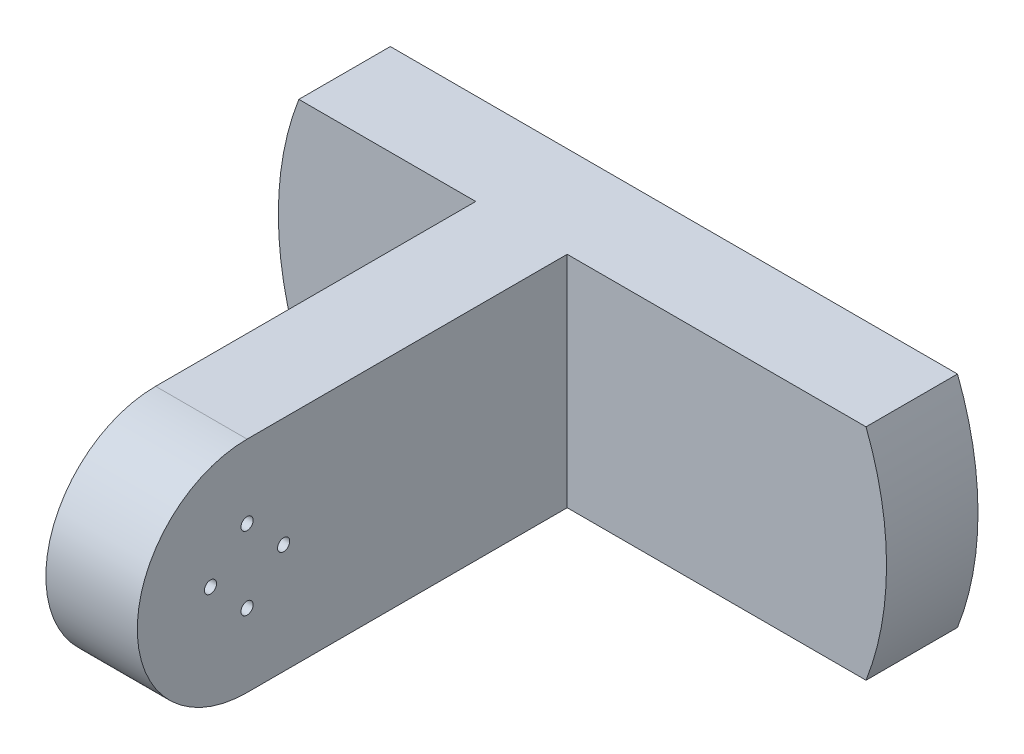
SolidWorks part; units mm, degrees
ref_plane "前视基准面" through (0, 0, 0) normal (0, 0, 1) x (1, 0, 0)
ref_plane "上视基准面" through (0, 0, 0) normal (0, 1, 0) x (1, 0, 0)
ref_plane "右视基准面" through (0, 0, 0) normal (1, 0, 0) x (0, 0, -1)
other "Configuration Table"
sketch "草图1" plane through (0, 0, 0) normal (0, 0, 1) x (1, 0, 0)
  line L0 (-47.6283, -3.2435) -> (-41.6283, -3.2435) construction
  line L1 (2.2417, -3.2435) -> (2.2417, 18.6189) construction
  line L2 (-41.6283, -3.2435) -> (44.1117, -3.2435) construction
  line L3 (44.1117, -3.2435) -> (46.1117, -3.2435) construction
  arc A0 (-47.6089, -1.8533) -> (-44.7236, 13.5277) centre (2.2417, -3.2435) cw
  arc A1 (45.1001, -4.2434) -> (43.3852, -15.2871) centre (2.2417, -3.2435) cw
  arc A2 (43.3852, 8.8001) -> (45.1001, -2.2436) centre (2.2417, -3.2435) cw
  arc A3 (-40.6116, -2.0485) -> (-38.1313, 11.1736) centre (2.2417, -3.2435) cw
  arc A4 (-38.1313, -17.6606) -> (-40.6116, -4.4385) centre (2.2417, -3.2435) cw
  circle A5 centre (-38.6097, -16.2435) radius 1
  circle A6 centre (-40.6283, -3.2435) radius 1
  circle A7 centre (-38.6097, 9.7565) radius 1
  circle A8 centre (43.0931, -16.2435) radius 1
  circle A9 centre (43.0931, 9.7565) radius 1
  circle A10 centre (45.1117, -3.2435) radius 1
  point P31 (-7.7583, -3.2435)
  dimension "D1" = 42.87
  dimension "D2" = 42.87
  dimension "D3" = 2
  dimension "D4" = 2
  dimension "D5" = 2
  dimension "D6" = 2
  dimension "D7" = 2
  dimension "D8" = 2
  dimension "D13" = 42.87
  dimension "D14" = 42.87
  dimension "D9" = 13
  dimension "D10" = 13
  dimension "D11" = 13
  dimension "D12" = 13
  dimension "D15" = 32.87
sketch "草图2" plane through (0, 0, 0) normal (0, 0, 1) x (1, 0, 0)
  line L0 (-47.6283, -3.2435) -> (52.1117, -3.2435) construction
  line L1 (-47.6283, 14.7565) -> (52.1117, 14.7565)
  line L2 (-47.6283, 14.7565) -> (-47.6283, -21.2435)
  line L3 (-47.6283, -21.2435) -> (52.1117, -21.2435)
  line L4 (52.1117, 14.7565) -> (52.1117, -21.2435)
  line L5 (2.2417, 14.7565) -> (2.2417, -21.2435)
  arc A0 (-44.7236, 13.5277) -> (-47.6089, -1.8533) centre (2.2417, -3.2435) ccw construction
  point P8 (2.2417, -3.2435)
  point P13 (-38.6097, 9.7565)
  dimension "D1" = 5
extrude "凸台-拉伸1" add sketch "草图2" along normal blind 15 contours L2 L0 L5 L1 | L0 L2 L3 L5 | L5 L0 L4 L1 | L0 L5 L3 L4 region at (-22.6933, 5.7565, 0) region at (-22.6933, -12.2435, 0) region at (27.1767, 5.7565, 0) region at (27.1767, -12.2435, 0)
sketch "草图3" plane through (0, 0, 0) normal (0, 0, 1) x (1, 0, 0)
  line L0 (2.2417, -3.2435) -> (2.2417, 18.6189) construction
  line L1 (-41.6283, -3.2435) -> (44.1117, -3.2435) construction
  line L2 (-47.6283, -3.2435) -> (-41.6283, -3.2435) construction
  line L3 (44.1117, -3.2435) -> (46.1117, -3.2435) construction
  line L4 (2.2417, -3.2435) -> (2.2417, 18.6189)
  line L5 (-41.6283, -3.2435) -> (44.1117, -3.2435)
  line L6 (-47.6283, -3.2435) -> (-41.6283, -3.2435)
  line L7 (44.1117, -3.2435) -> (46.1117, -3.2435)
  arc A0 (43.3852, -15.2871) -> (45.1001, -4.2434) centre (2.2417, -3.2435) ccw construction
  arc A1 (45.1001, -2.2436) -> (43.3852, 8.8001) centre (2.2417, -3.2435) ccw construction
  arc A2 (-44.7236, 13.5277) -> (-47.6089, -1.8533) centre (2.2417, -3.2435) ccw construction
  arc A3 (-40.6116, -4.4385) -> (-38.1313, -17.6606) centre (2.2417, -3.2435) ccw construction
  arc A4 (-38.1313, 11.1736) -> (-40.6116, -2.0485) centre (2.2417, -3.2435) ccw construction
  circle A5 centre (43.0931, -16.2435) radius 1 construction
  circle A6 centre (45.1117, -3.2435) radius 1 construction
  circle A7 centre (43.0931, 9.7565) radius 1 construction
  circle A8 centre (-38.6097, -16.2435) radius 1 construction
  circle A9 centre (-40.6283, -3.2435) radius 1 construction
  circle A10 centre (-38.6097, 9.7565) radius 1 construction
  arc A11 (43.3852, -15.2871) -> (45.1001, -4.2434) centre (2.2417, -3.2435) ccw
  arc A12 (45.1001, -2.2436) -> (43.3852, 8.8001) centre (2.2417, -3.2435) ccw
  arc A13 (-44.7236, 13.5277) -> (-47.6089, -1.8533) centre (2.2417, -3.2435) ccw
  arc A14 (-40.6116, -4.4385) -> (-38.1313, -17.6606) centre (2.2417, -3.2435) ccw
  arc A15 (-38.1313, 11.1736) -> (-40.6116, -2.0485) centre (2.2417, -3.2435) ccw
  circle A16 centre (43.0931, -16.2435) radius 1
  circle A17 centre (45.1117, -3.2435) radius 1
  circle A18 centre (43.0931, 9.7565) radius 1
  circle A19 centre (-38.6097, -16.2435) radius 1
  circle A20 centre (-40.6283, -3.2435) radius 1
  circle A21 centre (-38.6097, 9.7565) radius 1
  point P0 (-7.7583, -3.2435)
extrude "切除-拉伸1" cut sketch "草图3" along normal blind 5 contours A15 A21 | L5 A20 | L5 A20 | A14 A19 | A14 A19 | A16 | L7 A17 | L7 A17 | A18 | A15 A21 region at (-40.6283, -2.8191, 0) region at (43.0931, 9.7565, 0) region at (43.0931, -16.2435, 0) region at (45.1117, -2.8191, 0) region at (45.1117, -3.6679, 0) region at (-40.6283, -3.6679, 0) region at (-38.2032, -16.1142, 0) region at (-39.0121, -16.3716, 0) region at (-38.2032, 9.6272, 0) region at (-39.0121, 9.8846, 0)
sketch "草图4" plane through (0, 0, 0) normal (0, 0, -1) x (-1, 0, 0)
  line L0 (-48.75, 14.7565) -> (-52.1117, 14.7565)
  line L1 (44.2665, -21.2435) -> (47.6283, -21.2435)
  line L4 (-52.1117, -21.2435) -> (47.6283, -21.2435)
  line L5 (47.6283, -21.2435) -> (47.6283, 14.7565)
  line L6 (47.6283, 14.7565) -> (-52.1117, 14.7565)
  line L7 (-52.1117, 14.7565) -> (-52.1117, -21.2435)
  line L8 (-52.1117, -21.2435) -> (-48.75, -21.2435)
  line L9 (47.6283, -21.2435) -> (47.6283, 14.7565)
  line L10 (47.6283, 14.7565) -> (44.2665, 14.7565)
  line L11 (-52.1117, 14.7565) -> (-52.1117, -21.2435)
  arc A0 (-48.75, 14.7565) -> (-48.75, -21.2435) centre (-2.2417, -3.2435) ccw
  arc A1 (44.2665, -21.2435) -> (44.2665, 14.7565) centre (-2.2417, -3.2435) ccw
  line M12 (-52.1117, -21.2435) -> (47.6283, -21.2435)
  line M13 (47.6283, -21.2435) -> (47.6283, 14.7565)
  line M14 (47.6283, 14.7565) -> (-52.1117, 14.7565)
  line M15 (-52.1117, 14.7565) -> (-52.1117, -21.2435)
  dimension "D1" = 0
extrude "切除-拉伸2" cut sketch "草图4" against normal up to next contours A0 M14 M15 | A0 L11 M12 | A1 L9 M14 | A1 M12 M13 | L11 L8 A0 L0 region at (51.1093, 10.2874, 0) region at (-46.6258, 10.2874, 0) region at (51.1093, -16.7744, 0) region at (-46.6258, -16.7744, 0)
ref_plane "基准面1" through (-7.7583, -3.2435, 0) normal (1, 0, 0) x (0, 0, -1)
sketch "草图5" plane through (-7.7583, -3.2435, 0) normal (1, 0, 0) x (0, 0, -1)
  line L0 (-15, 0) -> (0, 0) construction
  line L1 (-7.5, -18) -> (-7.5, 32.1061) construction
  line L2 (-7.5, 0) -> (-67.5, 0) construction
  line L3 (-7.5, -18) -> (-67.5, -18)
  line L4 (-15, 18) -> (-15, -18)
  line L5 (-15, -18) -> (0, -18)
  line L6 (0, -18) -> (0, 18)
  line L7 (0, 18) -> (-15, 18)
  line L8 (-15, 18) -> (-15, -18)
  line L9 (-15, -18) -> (0, -18)
  line L10 (0, -18) -> (0, 0)
  line L11 (-7.5, 18) -> (-15, 18)
  line L12 (-7.5, 18) -> (-67.5, 18)
  arc A0 (-7.5, -18) -> (0, -16.3631) centre (-7.5, 0) ccw
  arc A1 (-67.5, 18) -> (-67.5, -18) centre (-67.5, 0) ccw
  point P8 (-7.5, 0)
  point P11 (-37.5, 0)
  dimension "D2" = 36
  dimension "D3" = 60
  dimension "D1" = 0
extrude "凸台-拉伸2" add sketch "草图5" along normal blind 7.5 and the other way blind 7.5 contours L12 A1 L3 L8 region at (-7.7583, -3.2435, 48.4397)
sketch "草图6" plane through (-15.2583, 0, 0) normal (-1, 0, 0) x (0, 0, 1)
  line L1 (67.5, 6.7565) -> (58.8397, 1.7565)
  line L2 (58.8397, 1.7565) -> (58.8397, -8.2435)
  line L3 (67.5, 14.7565) -> (15, 14.7565)
  line L4 (15, 14.7565) -> (15, -21.2435)
  line L5 (15, -21.2435) -> (67.5, -21.2435)
  line L6 (67.5, 14.7565) -> (15, 14.7565)
  line L7 (15, 14.7565) -> (15, -21.2435)
  line L8 (15, -21.2435) -> (67.5, -21.2435)
  line L9 (58.8397, -8.2435) -> (67.5, -13.2435)
  line L10 (67.5, -13.2435) -> (76.1603, -8.2435)
  line L11 (76.1603, -8.2435) -> (76.1603, 1.7565)
  line L12 (76.1603, 1.7565) -> (67.5, 6.7565)
  circle A0 centre (67.5, -3.2435) radius 10
  arc A1 (67.5, -21.2435) -> (67.5, 14.7565) centre (67.5, -3.2435) ccw
  arc A2 (67.5, -21.2435) -> (67.5, 14.7565) centre (67.5, -3.2435) ccw
  circle A3 centre (67.5, -3.2435) radius 8.6603 construction
  dimension "D2" = 20
  dimension "D1" = 0
extrude "切除-拉伸3" cut sketch "草图6" against normal blind 10 contours L11 L12 L1 L2 L9 L10 region at (-15.2583, -3.2435, 67.5)
sketch "草图7" plane through (-5.2583, 0, 0) normal (-1, 0, 0) x (0, 0, 1)
  line L3 (67.5, 14.7565) -> (15, 14.7565)
  line L4 (15, 14.7565) -> (15, -21.2435)
  line L5 (15, -21.2435) -> (67.5, -21.2435)
  line L6 (76.1603, -8.2435) -> (76.1603, 1.7565)
  line L7 (76.1603, 1.7565) -> (67.5, 6.7565)
  line L8 (67.5, 6.7565) -> (58.8397, 1.7565)
  line L9 (58.8397, 1.7565) -> (58.8397, -8.2435)
  line L10 (58.8397, -8.2435) -> (67.5, -13.2435)
  line L11 (67.5, -13.2435) -> (76.1603, -8.2435)
  line L12 (76.1603, -8.2435) -> (76.1603, 1.7565)
  line L13 (76.1603, 1.7565) -> (67.5, 6.7565)
  line L14 (67.5, 6.7565) -> (58.8397, 1.7565)
  line L15 (58.8397, 1.7565) -> (58.8397, -8.2435)
  line L16 (58.8397, -8.2435) -> (67.5, -13.2435)
  line L17 (67.5, -13.2435) -> (76.1603, -8.2435)
  line L18 (67.5, 14.7565) -> (15, 14.7565)
  line L19 (15, 14.7565) -> (15, -21.2435)
  line L20 (15, -21.2435) -> (67.5, -21.2435)
  circle A0 centre (67.5, -3.2435) radius 6 construction
  arc A1 (67.5, -21.2435) -> (67.5, 14.7565) centre (67.5, -3.2435) ccw
  arc A2 (67.5, -21.2435) -> (67.5, 14.7565) centre (67.5, -3.2435) ccw
  circle A3 centre (67.5, 2.7565) radius 1
  circle A4 centre (73.5, -3.2435) radius 1
  circle A5 centre (61.5, -3.2435) radius 1
  circle A6 centre (67.5, -9.2435) radius 1
  dimension "D3" = 12
  dimension "D4" = 2
  dimension "D5" = 2
  dimension "D6" = 2
  dimension "D7" = 2
  dimension "D1" = 0
  dimension "D2" = 0
extrude "切除-拉伸4" cut sketch "草图7" against normal blind 5 contours A5 | A4 | A3 | A6 region at (-5.2583, 2.7565, 67.5) region at (-5.2583, -3.2435, 73.5) region at (-5.2583, -3.2435, 61.5) region at (-5.2583, -9.2435, 67.5)
